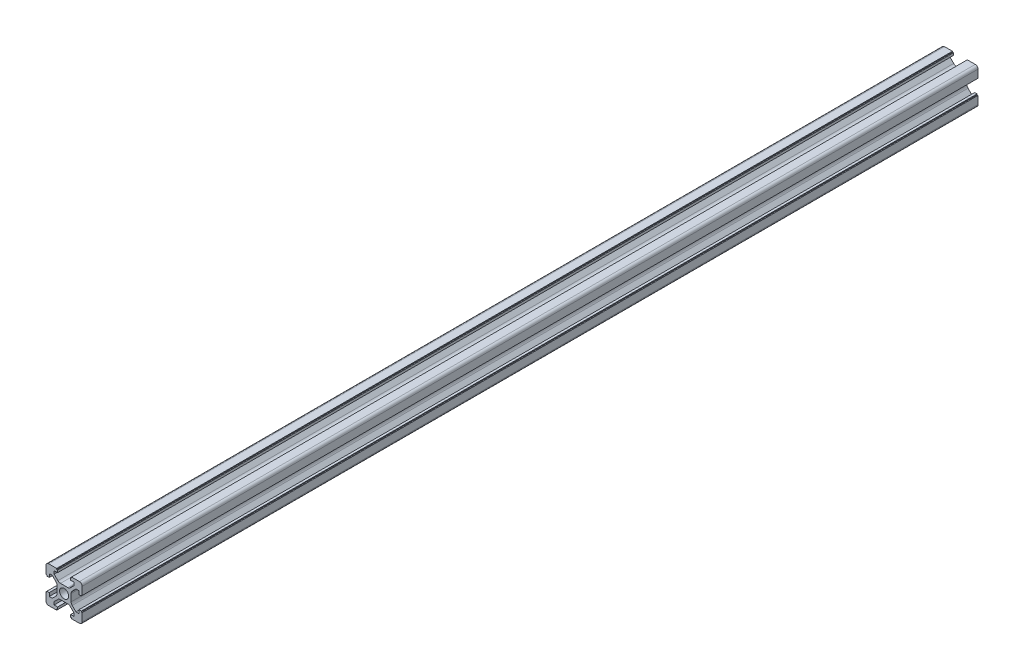
SolidWorks part; units mm, degrees
material "6063-O"
ref_plane "Front Plane" through (0, 0, 0) normal (0, 0, 1) x (1, 0, 0)
ref_plane "Top Plane" through (0, 0, 0) normal (0, 1, 0) x (1, 0, 0)
ref_plane "Right Plane" through (0, 0, 0) normal (1, 0, 0) x (0, 0, -1)
sketch "Sketch1" plane through (0, 0, 0) normal (0, 0, 1) x (1, 0, 0)
  line L0 (10, -4.1) -> (10, -8.5)
  line L1 (4.1, 10) -> (8.5, 10)
  line L2 (8.5, -10) -> (4.1, -10)
  line L3 (-8.5, -10) -> (-4.1, -10)
  line L4 (10, 8.5) -> (10, 4.1)
  line L7 (8.5, 10) -> (4.1, 10)
  line L8 (5.5, 6.5607) -> (3.4251, 4.4858)
  line L9 (8.5, 10) -> (4.1, 10)
  line L10 (3.9, 2.0109) -> (3.9, -2.0109)
  line L11 (2.0109, -3.9) -> (-2.0109, -3.9)
  line L12 (-3.9, -2.0109) -> (-3.9, 2.0109)
  line L13 (-2.0109, 3.9) -> (2.8393, 3.9)
  line L14 (2.5, 0) -> (22.2403, 0) construction
  line L15 (3.6, 9.5) -> (3.6, 8.2)
  line L16 (9.5, 3.6) -> (8.2, 3.6)
  line L17 (8.2, 3.6) -> (8.2, 5.5)
  line L18 (8.2, 5.5) -> (6.5607, 5.5)
  line L19 (10, -4.1) -> (10, -8.5)
  line L20 (4.1, 9.5) -> (3.6, 9.5)
  line L21 (4.1, 10) -> (4.1, 9.5)
  line L22 (8.5, 10) -> (4.1, 10)
  line L23 (10, 4.1) -> (9.5, 4.1)
  line L24 (9.5, 4.1) -> (9.5, 3.6)
  line L25 (5.5, 8.2) -> (5.5, 6.5607)
  line L26 (3.6, 8.2) -> (5.5, 8.2)
  line L27 (4.4858, 3.4251) -> (6.5607, 5.5)
  line L28 (10, -8.5) -> (10, -4.1)
  line L29 (6.5607, -5.5) -> (4.4858, -3.4251)
  line L30 (10, -8.5) -> (10, -4.1)
  line L31 (2.0109, -3.9) -> (-2.0109, -3.9)
  line L32 (3.9, 2.8393) -> (3.9, -2.0109)
  line L33 (9.5, -3.6) -> (8.2, -3.6)
  line L34 (3.6, -9.5) -> (3.6, -8.2)
  line L35 (3.6, -8.2) -> (5.5, -8.2)
  line L36 (5.5, -8.2) -> (5.5, -6.5607)
  line L37 (9.5, -4.1) -> (9.5, -3.6)
  line L38 (10, -4.1) -> (9.5, -4.1)
  line L39 (10, -8.5) -> (10, -4.1)
  line L40 (4.1, -10) -> (4.1, -9.5)
  line L41 (4.1, -9.5) -> (3.6, -9.5)
  line L42 (8.2, -5.5) -> (6.5607, -5.5)
  line L43 (8.2, -3.6) -> (8.2, -5.5)
  line L44 (3.4251, -4.4858) -> (5.5, -6.5607)
  line L45 (-4.1, -10) -> (-8.5, -10)
  line L46 (-10, -8.5) -> (-10, -4.1)
  line L47 (-8.5, -10) -> (-4.1, -10)
  line L48 (-5.5, -6.5607) -> (-3.4251, -4.4858)
  line L49 (-8.5, -10) -> (-4.1, -10)
  line L50 (-3.9, -2.0109) -> (-3.9, 2.0109)
  line L51 (2.0109, -3.9) -> (-2.0109, -3.9)
  line L52 (-3.6, -9.5) -> (-3.6, -8.2)
  line L53 (-9.5, -3.6) -> (-8.2, -3.6)
  line L54 (-8.2, -3.6) -> (-8.2, -5.5)
  line L55 (-8.2, -5.5) -> (-6.5607, -5.5)
  line L56 (-4.1, -9.5) -> (-3.6, -9.5)
  line L57 (-4.1, -10) -> (-4.1, -9.5)
  line L58 (-8.5, -10) -> (-4.1, -10)
  line L59 (-10, -4.1) -> (-9.5, -4.1)
  line L60 (-9.5, -4.1) -> (-9.5, -3.6)
  line L61 (-5.5, -8.2) -> (-5.5, -6.5607)
  line L62 (-3.6, -8.2) -> (-5.5, -8.2)
  line L63 (-4.4858, -3.4251) -> (-6.5607, -5.5)
  line L64 (-10, 4.1) -> (-10, 8.5)
  line L65 (-8.5, 10) -> (-4.1, 10)
  line L66 (-10, 8.5) -> (-10, 4.1)
  line L67 (-6.5607, 5.5) -> (-4.4858, 3.4251)
  line L68 (-10, 8.5) -> (-10, 4.1)
  line L69 (-2.0109, 3.9) -> (2.0109, 3.9)
  line L70 (-3.9, -2.0109) -> (-3.9, 2.0109)
  line L71 (-9.5, 3.6) -> (-8.2, 3.6)
  line L72 (-3.6, 9.5) -> (-3.6, 8.2)
  line L73 (-3.6, 8.2) -> (-5.5, 8.2)
  line L74 (-5.5, 8.2) -> (-5.5, 6.5607)
  line L75 (-9.5, 4.1) -> (-9.5, 3.6)
  line L76 (-10, 4.1) -> (-9.5, 4.1)
  line L77 (-10, 8.5) -> (-10, 4.1)
  line L78 (-4.1, 10) -> (-4.1, 9.5)
  line L79 (-4.1, 9.5) -> (-3.6, 9.5)
  line L80 (-8.2, 5.5) -> (-6.5607, 5.5)
  line L81 (-8.2, 3.6) -> (-8.2, 5.5)
  line L82 (-3.4251, 4.4858) -> (-5.5, 6.5607)
  line L83 (4.1, -10) -> (8.5, -10)
  arc A0 (2.0109, -3.9) -> (3.4251, -4.4858) centre (2.0109, -5.9) cw
  arc A1 (4.4858, -3.4251) -> (3.9, -2.0109) centre (5.9, -2.0109) cw
  arc A2 (3.9, 2.0109) -> (4.4858, 3.4251) centre (5.9, 2.0109) cw
  arc A3 (2.0109, 3.9) -> (3.4251, 4.4858) centre (2.0109, 5.9) ccw
  arc A4 (-2.0109, 3.9) -> (-3.4251, 4.4858) centre (-2.0109, 5.9) cw
  arc A5 (-4.4858, 3.4251) -> (-3.9, 2.0109) centre (-5.9, 2.0109) cw
  arc A6 (-3.4251, -4.4858) -> (-2.0109, -3.9) centre (-2.0109, -5.9) cw
  arc A7 (-3.9, -2.0109) -> (-4.4858, -3.4251) centre (-5.9, -2.0109) cw
  circle A8 centre (0, 0) radius 2.5
  arc A9 (-8.5, -10) -> (-10, -8.5) centre (-8.5, -8.5) cw
  arc A10 (-10, 8.5) -> (-8.5, 10) centre (-8.5, 8.5) cw
  arc A11 (8.5, 10) -> (10, 8.5) centre (8.5, 8.5) cw
  arc A12 (8.5, -10) -> (10, -8.5) centre (8.5, -8.5) ccw
  point P0 (0, 0)
  point P86 (0, 0)
  point P107 (10, -10)
  dimension "D3" = 2
  dimension "D5" = 5
  dimension "D2" = 1.5
  dimension "D8" = 1.5
  dimension "D6" = 4
  dimension "D7" = 6.1
  dimension "D11" = 0.5
  dimension "D12" = 0.5
extrude "Boss-Extrude2" add sketch "Sketch1" along normal blind 495 contours L2 A12 L0 L38 L37 L33 L43 L42 L29 A1 L10 A2 L27 L18 L17 L16 L24 L23 L4 A11 L1 L21 L20 L15 L26 L25 L8 A3 L13 A4 L82 L74 L73 L72 L79 L78 L65 A10 L64 L76 L75 L71 L81 L80 L67 A5 L12 region at (9.7172, -6.3, 0)
